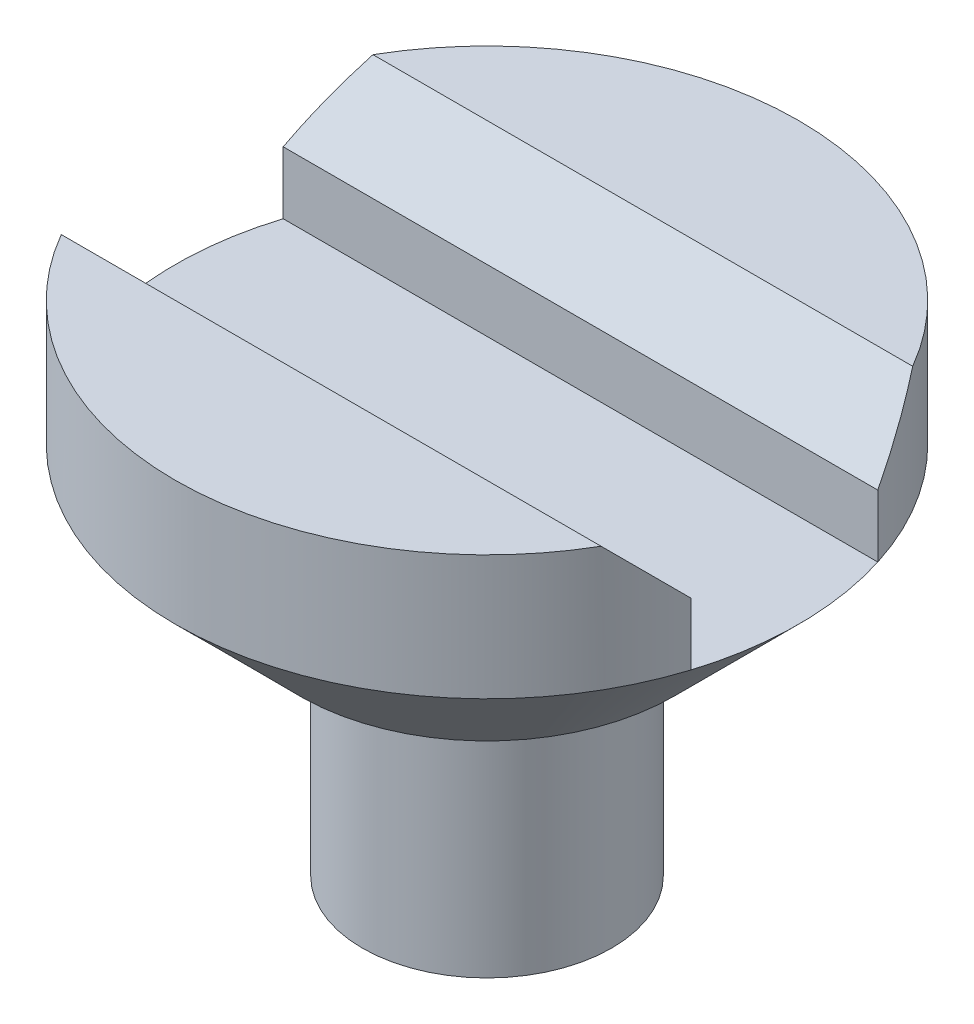
SolidWorks part; units mm, degrees
ref_plane "Front Plane" through (0, 0, 0) normal (0, 0, 1) x (1, 0, 0)
ref_plane "Top Plane" through (0, 0, 0) normal (0, 1, 0) x (1, 0, 0)
ref_plane "Right Plane" through (0, 0, 0) normal (1, 0, 0) x (0, 0, -1)
sketch "Sketch1" plane through (0, 0, 0) normal (0, 0, 1) x (1, 0, 0)
  line L0 (0, 0) -> (0, 101.6)
  line L1 (0, 101.6) -> (63.5, 101.6)
  line L2 (63.5, 101.6) -> (63.5, 50.8)
  line L3 (63.5, 50.8) -> (25.4, 50.8)
  line L4 (25.4, 50.8) -> (25.4, 0)
  line L5 (25.4, 0) -> (0, 0)
  dimension "D1" = 25.4
  dimension "D2" = 63.5
  dimension "D3" = 50.8
  dimension "D4" = 101.6
revolve "Revolve1" add sketch "Sketch1" angle 360 about L0
sketch "Sketch2" plane through (0, 101.6, 0) normal (0, 1, 0) x (1, 0, 0)
  line L1 (88.9, -19.05) -> (-88.9, -19.05)
  line L2 (88.9, -19.05) -> (88.9, 19.05)
  line L3 (88.9, 19.05) -> (-88.9, 19.05)
  line L4 (-88.9, -19.05) -> (-88.9, 19.05)
  line L5 (88.9, -19.05) -> (-88.9, 19.05) construction
  line L6 (88.9, 19.05) -> (-88.9, -19.05) construction
  point P0 (0, 0)
  dimension "D1" = 38.1
  dimension "D2" = 177.8
extrude "Cut-Extrude1" cut sketch "Sketch2" against normal blind 25.4
chamfer "Chamfer1" distance 12.7 angle 45 2 edges at (0, 101.6, -19.05) (0, 101.6, 19.05)
chamfer "Chamfer2" distance 25.4 angle 45 1 edges at (0, 50.8, -63.5)
